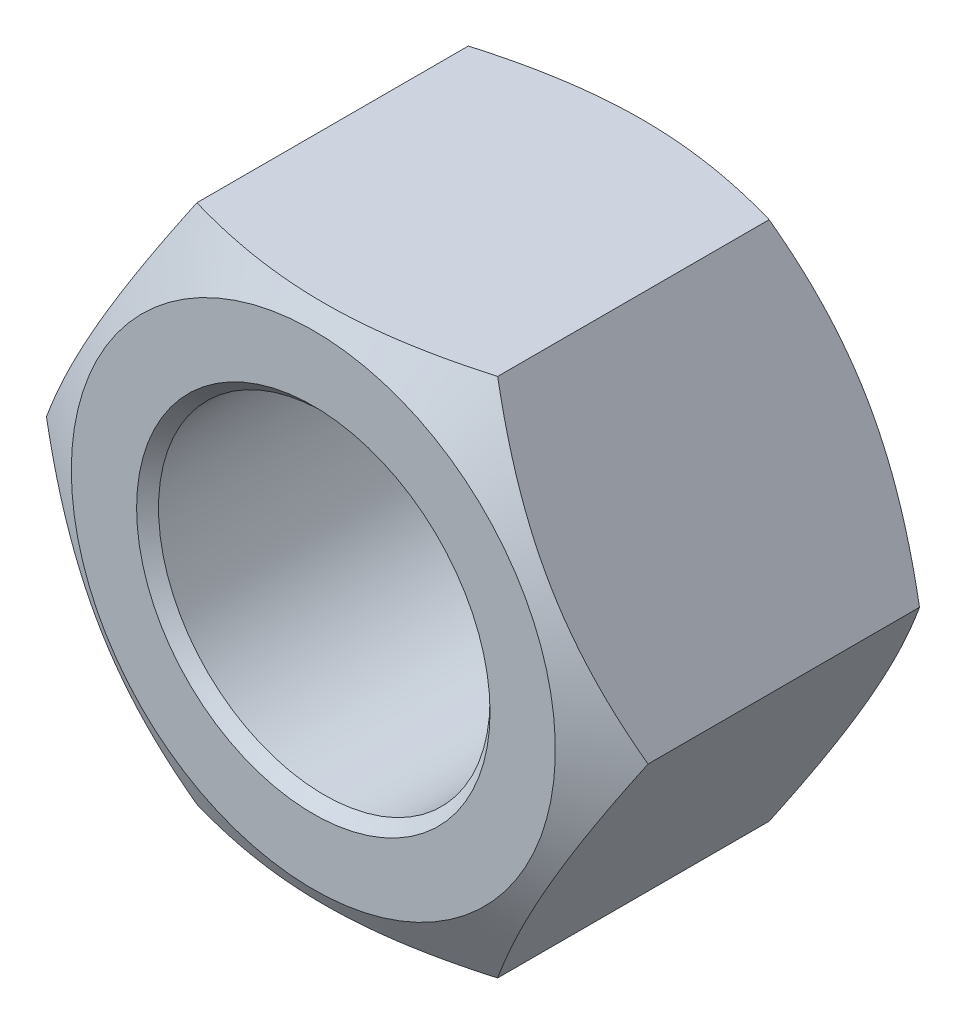
SolidWorks part; units mm, degrees
ref_plane "Front" through (0, 0, 0) normal (0, 0, 1) x (1, 0, 0)
ref_plane "Top" through (0, 0, 0) normal (0, 1, 0) x (1, 0, 0)
ref_plane "Right" through (0, 0, 0) normal (1, 0, 0) x (0, 0, -1)
sketch "Sketch1" plane through (0, 0, 0) normal (0, 0, 1) x (1, 0, 0)
  line L1 (15.8771, -27.5) -> (31.7543, 0)
  line L2 (31.7543, 0) -> (15.8771, 27.5)
  line L3 (15.8771, 27.5) -> (-15.8771, 27.5)
  line L4 (-15.8771, 27.5) -> (-31.7543, 0)
  line L5 (-31.7543, 0) -> (-15.8771, -27.5)
  line L6 (-15.8771, -27.5) -> (15.8771, -27.5)
  circle A0 centre (0, 0) radius 27.5 construction
  circle A1 centre (0, 0) radius 17.5
  dimension "D1" = 35
extrude "BaseNut" add sketch "Sketch1" against normal blind 34.7
cosmetic thread "ThreadCosmetic1" [suppressed] parameters "D2"=37
sketch "Sketch2" plane through (15.0481, 0, -16.7061) normal (0, 1, 0) x (0, 0, -1)
  line L0 (-23.7227, 15.0481) -> (22.0646, 15.0481) construction
  line L2 (17.9939, 46.8024) -> (17.9939, 30.9252) construction
  line L4 (17.9939, 46.8024) -> (-16.7061, 46.8024) construction
  line L8 (15.5376, 46.8024) -> (17.9939, 42.5481)
  line L9 (17.9939, 46.8024) -> (15.5376, 46.8024)
  line L10 (17.9939, 42.5481) -> (17.9939, 46.8024)
  dimension "D1" = 30
  dimension "s1" = 55
revolve "Chamfer1" cut sketch "Sketch2" angle 360 about L0
sketch "Sketch6" plane through (-9.1975, 0, -10.2525) normal (0, 1, 0) x (0, 0, 1)
  line L0 (23.3574, 9.1975) -> (-22.3023, 9.1975) construction
  line L2 (-24.4475, 26.6975) -> (-24.4475, 28.6475)
  line L4 (-24.4475, 28.6475) -> (-23.3216, 26.6975)
  line L6 (-23.3216, 26.6975) -> (-24.4475, 26.6975)
  dimension "da" = 38.9
  dimension "D2" = 60
revolve "EndChamfer1" cut sketch "Sketch6" angle 360 about L0
sketch "Sketch5" plane through (-14.793, 0, -16.9612) normal (0, 1, 0) x (0, 0, 1)
  line L0 (-22.5748, 14.793) -> (24.743, 14.793) construction
  line L2 (16.9612, 40.343) -> (16.9612, 46.5473)
  line L4 (16.9612, 46.5473) -> (13.3792, 46.5473)
  line L6 (13.3792, 46.5473) -> (16.9612, 40.343)
  dimension "dw1" = 51.1
  dimension "D2" = 30
revolve "Chamfer2" cut sketch "Sketch5" angle 360 about L0
sketch "Sketch3" plane through (-20.9491, 1.8856, 0) normal (0, 0, 1) x (1, 0, 0)
  circle A1 centre (20.9491, -1.8856) radius 17.5 construction
  circle A2 centre (20.9491, -1.8856) radius 25.55
  circle A3 centre (20.9491, -1.8856) radius 17.5
  dimension "dw" = 51.1
extrude "Extrude1" [suppressed] add sketch "Sketch3" along normal blind 0.8
chamfer "EndChamfer3" [suppressed] distance 1.1567 angle 45
chamfer "EndChamfer2" distance 1.1567 angle 45 1 edges at (17.5, 0, 0)
sketch "Sketch7" plane through (0, 0, 0) normal (0, 1, 0) x (1, 0, 0)
  line L0 (0, 48.6183) -> (0, -13.0076) construction
  line L1 (16.5, 34.0742) -> (17.5, 34.0742)
  line L2 (17.5, 34.0742) -> (18.366, 33.5742)
  line L3 (18.366, 33.5742) -> (17.5, 33.0742)
  line L4 (17.5, 33.0742) -> (16.5, 33.0742)
  line L5 (16.5, 33.0742) -> (16.5, 34.0742)
  line L6 (17.5, 33.5742) -> (-17.5, 33.5742) construction
  dimension "D2" = 35
revolve "Cut-Revolve10" [suppressed] cut sketch "Sketch7" angle 360 about L0
pattern_linear "LPattern10" [suppressed] count 28 spacing 1.2 along (0, 0, 1) of bodies 106
equation "\"D1@EndChamfer3\" = \"m@BaseNut\" / 30"
equation "\"D1@EndChamfer2\" = \"m@BaseNut\" / 30"
equation "\"s1@Sketch2\" = \"s@Sketch1\""
equation "\"D2@Sketch7\" = \"D1@Sketch1\""
equation "\"D1@Sketch7\" = (  \"D2@ThreadCosmetic1\" - \"D1@Sketch1\" )  / 2"
equation "\"D3@LPattern10\" = \"D1@Sketch7\" * 1.2"
equation "\"D1@LPattern10\" = \"m@BaseNut\" / \"D3@LPattern10\" - 1"
